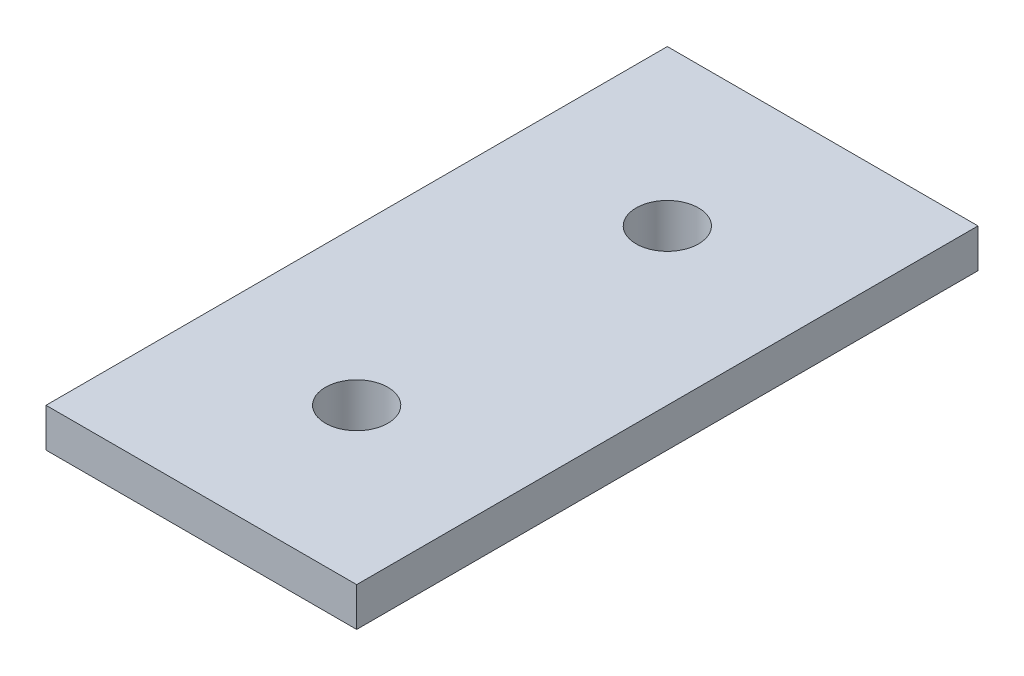
SolidWorks part; units mm, degrees
ref_plane "Front Plane" through (0, 0, 0) normal (0, 0, 1) x (1, 0, 0)
ref_plane "Top Plane" through (0, 0, 0) normal (0, 1, 0) x (1, 0, 0)
ref_plane "Right Plane" through (0, 0, 0) normal (1, 0, 0) x (0, 0, -1)
sketch "Sketch1" plane through (0, 0, 0) normal (0, 1, 0) x (1, 0, 0)
  line L0 (-11.1125, 23.8125) -> (11.1125, 23.8125)
  line L1 (-12.7, -25.4) -> (12.7, -25.4)
  line L2 (-12.7, -25.4) -> (-12.7, 25.4)
  line L3 (-12.7, 25.4) -> (12.7, 25.4)
  line L4 (12.7, -25.4) -> (12.7, 25.4)
  line L5 (-12.7, -25.4) -> (12.7, 25.4) construction
  line L6 (-12.7, 25.4) -> (12.7, -25.4) construction
  line L7 (11.1125, -23.8125) -> (11.1125, 23.8125)
  line L8 (-11.1125, -23.8125) -> (11.1125, -23.8125)
  line L9 (-11.1125, -23.8125) -> (-11.1125, 23.8125)
  line L10 (-10.8585, 23.5585) -> (10.8585, 23.5585)
  line L11 (10.8585, -23.5585) -> (10.8585, 23.5585)
  line L12 (-10.8585, -23.5585) -> (10.8585, -23.5585)
  line L13 (-10.8585, -23.5585) -> (-10.8585, 23.5585)
  point P0 (0, 0)
  dimension "D1" = 50.8
  dimension "D2" = 25.4
  dimension "D3" = 1.5875
  dimension "D4" = 0.254
extrude "Boss-Extrude1" add sketch "Sketch1" along normal blind 0.762 contours L13 L12 L11 L10 region at (0, 0, 0)
sketch "Sketch2" plane through (0, 0.762, 0) normal (0, 1, 0) x (1, 0, 0)
  line L1 (-12.7, -25.4) -> (12.7, -25.4)
  line L2 (-12.7, -25.4) -> (-12.7, 25.4)
  line L3 (-12.7, 25.4) -> (12.7, 25.4)
  line L4 (12.7, -25.4) -> (12.7, 25.4)
  line L5 (-12.7, -25.4) -> (12.7, 25.4) construction
  line L6 (-12.7, 25.4) -> (12.7, -25.4) construction
  point P0 (0, 0)
  dimension "D1" = 25.4
  dimension "D2" = 50.8
extrude "Boss-Extrude2" add sketch "Sketch2" along normal blind 3.175
sketch "Sketch3" plane through (0, 3.937, 0) normal (0, 1, 0) x (1, 0, 0)
  line L0 (-12.7, 25.4) -> (-12.7, -25.4) construction
  line L1 (-12.7, 0) -> (12.7, 0) construction
  line L2 (12.7, -25.4) -> (12.7, 25.4) construction
  circle A0 centre (0, 12.7) radius 2.5527
  circle A1 centre (0, -12.7) radius 2.5527
  dimension "D1" = 5.1054
  dimension "D2" = 12.7
  dimension "D3" = 12.7
extrude "Cut-Extrude1" cut sketch "Sketch3" against normal through all
